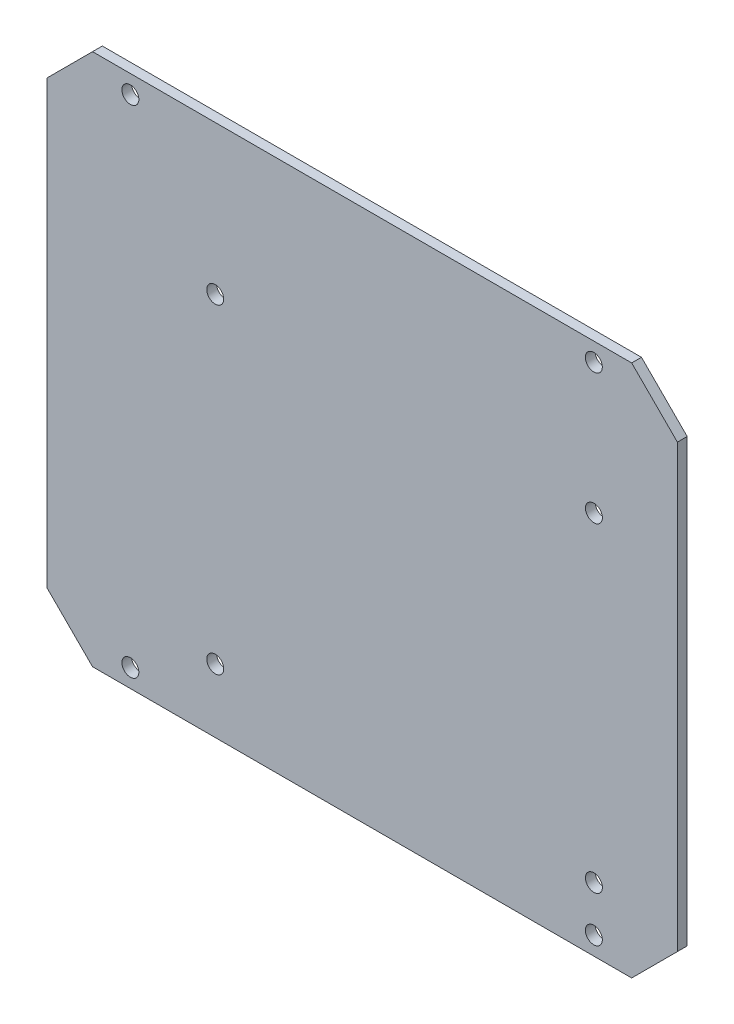
SolidWorks part; units mm, degrees
ref_plane "前视基准面" through (0, 0, 0) normal (0, 0, 1) x (1, 0, 0)
ref_plane "上视基准面" through (0, 0, 0) normal (0, 1, 0) x (1, 0, 0)
ref_plane "右视基准面" through (0, 0, 0) normal (1, 0, 0) x (0, 0, -1)
sketch "草图2" plane through (0, 0, -39) normal (0, 0, -1) x (-1, 0, 0)
  line L32 (-47.3467, -34.0538) -> (-40.3426, -41.058)
  line L33 (-40.3426, -41.058) -> (42.2491, -41.058)
  line L34 (42.2491, -41.058) -> (49.2533, -34.0538)
  line L35 (49.2533, -34.0538) -> (49.2533, 33.5378)
  line L36 (49.2533, 33.5378) -> (42.2491, 40.542)
  line L37 (-47.3467, 33.5378) -> (-47.3467, -34.0538)
  line L38 (-40.3426, 40.542) -> (-47.3467, 33.5378)
  line L39 (42.2491, 40.542) -> (-40.3426, 40.542)
  line L40 (-47.3467, -34.0538) -> (-40.3426, -41.058)
  line L41 (-40.3426, -41.058) -> (42.2491, -41.058)
  line L42 (42.2491, -41.058) -> (49.2533, -34.0538)
  line L43 (49.2533, -34.0538) -> (49.2533, 33.5378)
  line L44 (49.2533, 33.5378) -> (42.2491, 40.542)
  line L45 (-47.3467, 33.5378) -> (-47.3467, -34.0538)
  line L46 (-40.3426, 40.542) -> (-47.3467, 33.5378)
  line L47 (42.2491, 40.542) -> (-40.3426, 40.542)
  dimension "D1" = 0.2
extrude "凸台-拉伸1" add sketch "草图2" along normal blind 1.5
sketch "草图3" plane through (0, 0, -40.5) normal (0, 0, -1) x (-1, 0, 0)
  circle A0 centre (-34.5467, -38.258) radius 1.3
  circle A1 centre (36.4533, -38.258) radius 1.3
  circle A2 centre (-34.5467, 37.742) radius 1.3
  circle A3 centre (36.4533, 37.742) radius 1.3
  dimension "D1" = 2.6
extrude "切除-拉伸1" cut sketch "草图3" against normal through all
sketch "草图4" plane through (0, 0, -40.5) normal (0, 0, -1) x (-1, 0, 0)
  circle A1 centre (23.4533, -31.2932) radius 1.3
  circle A2 centre (23.4533, -31.2932) radius 1.3
  circle A3 centre (-34.5583, -31.2932) radius 1.3
  circle A4 centre (-34.5583, -31.2932) radius 1.3
  circle A5 centre (23.4533, 17.742) radius 1.3
  circle A6 centre (23.4533, 17.742) radius 1.3
  circle A7 centre (-34.5583, 17.742) radius 1.3
  circle A8 centre (-34.5583, 17.742) radius 1.3
  dimension "D1" = 0
  dimension "D2" = 0
  dimension "D3" = 0
  dimension "D4" = 0
extrude "切除-拉伸2" cut sketch "草图4" against normal up to next
